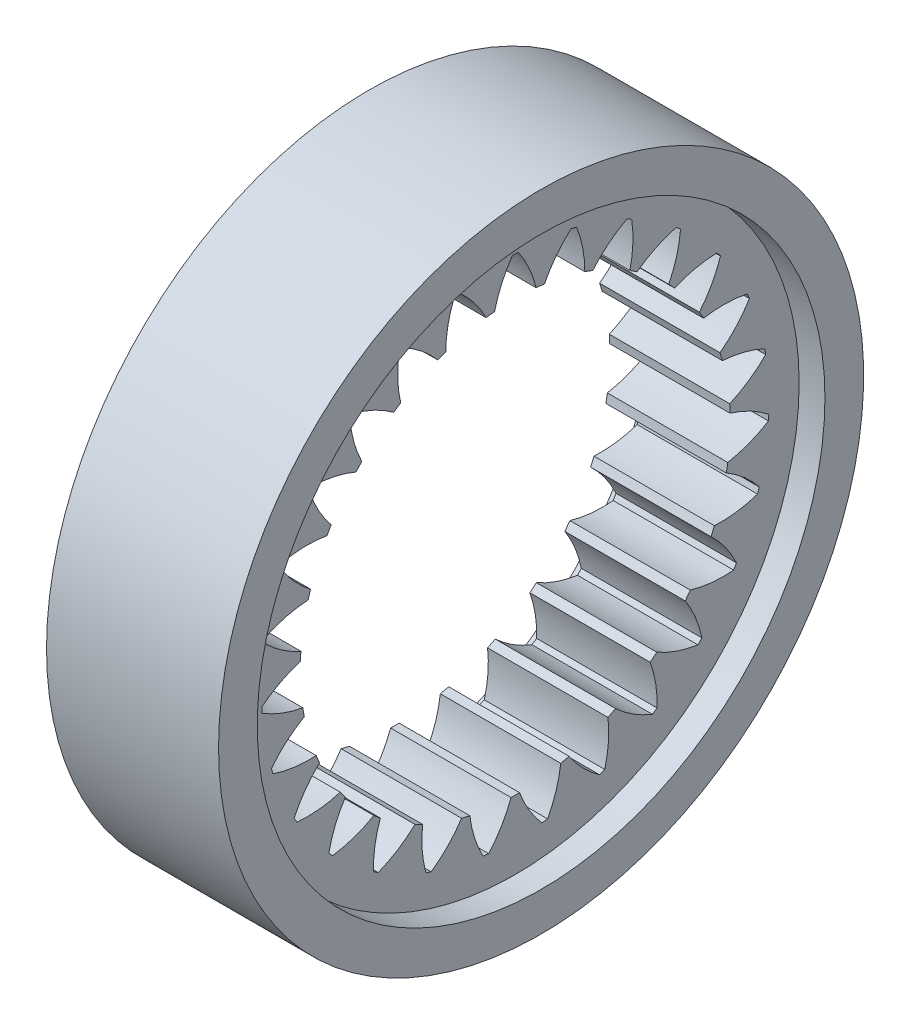
SolidWorks part; units mm, degrees
ref_plane "Plane1" through (0, 0, 0) normal (0, 0, 1) x (1, 0, 0)
ref_plane "Plane2" through (0, 0, 0) normal (0, 1, 0) x (1, 0, 0)
ref_plane "Plane3" through (0, 0, 0) normal (1, 0, 0) x (0, 0, -1)
other "Configuration Table"
sketch "HoldingSke" plane through (0, 0, 0) normal (0, 1, 0) x (1, 0, 0)
  line L0 (0, 0) -> (0.4455, -0.227)
  line L1 (-15, 0) -> (100, 0) construction
  line L2 (0, 0) -> (-2.1039, 2.3779)
  line L3 (0, 0) -> (-11.863, 4.5341)
  line L4 (0, 0) -> (7.6947, 3.9207)
  line L5 (0, 0) -> (-23.7986, -8.8762)
  line L6 (0, 0) -> (-10.5278, -7.1032)
  line L7 (-2.1039, 2.3779) -> (3.3635, 27.1825)
  line L8 (-76.2, 4.3779) -> (-54.61, 4.3779)
  line L9 (-71.009, 38.7566) -> (-53.1078, 45.2721)
  line L10 (-76.2, 71.12) -> (104.1128, 71.12)
  line L11 (0, 0) -> (-20, 0)
  line L12 (-76.2, 101.6) -> (-76.133, 101.6)
  line L13 (24.9733, 27.94) -> (52.9518, 28.4284)
  line L14 (24.9733, 27.94) -> (24.9743, 27.94)
  line L15 (24.9733, 27.94) -> (100.4006, 29.5858)
  circle A0 centre (0, 0) radius 37.5
  circle A1 centre (0, 0) radius 12.7
  circle A2 centre (0, 0) radius 12.7
  dimension "Num_teeth" = 27
  dimension "Pitch_radius" = 180.3128
  dimension "Width" = 20
  dimension "Diameter" = 75
sketch "BasProSke" plane through (0, 0, 0) normal (0, 1, 0) x (1, 0, 0)
  line L0 (-10, 0) -> (60, 0) construction
  line L1 (0, 25) -> (0, 37.5)
  line L2 (0, 25) -> (20, 25)
  line L3 (20, 25) -> (20, 37.5)
  line L4 (20, 37.5) -> (0, 37.5)
  dimension "Thickness" = 20
  dimension "Diameter" = 75
revolve "Base-Revolve" add sketch "BasProSke" angle 360 about L0
sketch "TooCutSke" plane through (0, 0, 0) normal (1, 0, 0) x (0, 0, -1)
  line L3 (1.7374, 26.944) -> (1.7374, 53.6633) construction
  line L4 (0, 0) -> (0, 59.563) construction
  line L5 (0, 0) -> (-7.9323, 67.8655) construction
  line L6 (-10.7181, 21.7372) -> (34.936, 27.0734) construction
  circle A0 centre (0, 0) radius 27 construction
  circle A1 centre (0, 0) radius 29.501 construction
  circle A2 centre (0, 0) radius 22.8345 construction
  circle A3 centre (0, 0) radius 24.9746 construction
  arc A4 (2.4164, 24.8574) -> (0.3274, 29.4992) centre (-10.7181, 21.7372) ccw
  arc A5 (2.4164, 24.8574) -> (-2.4164, 24.8574) centre (0, 0) ccw
  arc A6 (0.3274, 29.4992) -> (-0.3274, 29.4992) centre (0, 0) ccw
  arc A7 (-0.3274, 29.4992) -> (-2.4164, 24.8574) centre (10.7181, 21.7372) ccw
extrude "ToothCut" cut sketch "TooCutSke" along normal through all
fillet "Breaks" [suppressed] radius 0.2
fillet "RootFillets" [suppressed] radius 0.501
pattern_circular "TeethCuts" count 27 every 13.333 about axis through (-10, 0, 0) along (1, 0, 0) of "RootFillets", "Breaks", "ToothCut"
sketch "Sketch1" plane through (20, 0, 0) normal (1, 0, 0) x (0, 0, -1)
  circle A0 centre (0, 0) radius 33
  dimension "D1" = 66
extrude "Cut-Extrude1" cut sketch "Sketch1" against normal blind 3
sketch "Sketch2" plane through (0, 0, 0) normal (-1, 0, 0) x (0, 0, 1)
  circle A0 centre (0, 0) radius 33
  dimension "D1" = 66
extrude "Cut-Extrude2" cut sketch "Sketch2" against normal blind 3
equation "' \"Module@HoldingSke\" = 6.35"
equation "' \"Num_teeth@HoldingSke\" = 24"
equation "' \"Ap@HoldingSke\" =  14.5"
equation "' \"Ap@HoldingSke\" = 14.5"
equation "' \"Width@HoldingSke\" = 12"
equation "' \"Diameter@HoldingSke\" = 8 * 25.4"
equation "' \"Show_teeth@HoldingSke\" = 100"
equation "' \"Backlash@HoldingSke\" = 0.009 * 25.4"
equation "' \"Addendum_fac@HoldingSke\" = 1.0"
equation "' \"Dedendum_fac@HoldingSke\" = 1.25"
equation "' \"Dedendum_add@HoldingSke\" = 0.00005 * 25.4"
equation "' \"Clearance_fac@HoldingSke\" = 0.25"
equation "\"Pitch@HoldingSke\" = 1 / \"Module@HoldingSke\" "
equation "\"Overcut_dia@TooCutSke\" = (\"Num_teeth@HoldingSke\" - 2 * \"Addendum_fac@HoldingSke\") / \"Pitch@HoldingSke\" - 0.002 * 25.4"
equation "\"Pitch_dia@TooCutSke\" = \"Num_teeth@HoldingSke\" / \"Pitch@HoldingSke\""
equation "\"Base_dia@TooCutSke\" = \"Num_teeth@HoldingSke\" / \"Pitch@HoldingSke\" * cos((\"Ap@HoldingSke\"  * 3.14159265 / 180)) * 0.90"
equation "\"Root_dia@TooCutSke\" = \"Num_teeth@HoldingSke\"  / \"Pitch@HoldingSke\" + 2 *  \"Dedendum_fac@HoldingSke\"/ \"Pitch@HoldingSke\" + \"Dedendum_add@HoldingSke\" * 2"
equation "\"Half_ang@TooCutSke\" = 180 / \"Num_teeth@HoldingSke\""
equation "\"Half_CT@TooCutSke\" = \"Num_teeth@HoldingSke\" / \"Pitch@HoldingSke\" * sin((3.14159265 / 2 / \"Num_teeth@HoldingSke\")) / 2 + 10 * \"Backlash@HoldingSke\" / 4"
equation "\"Flank_rad@TooCutSke\" = \"Num_teeth@HoldingSke\" / \"Pitch@HoldingSke\" / 4"
equation "\"Radius@RootFillets\"= \"Clearance_fac@HoldingSke\" / \"Pitch@HoldingSke\" + \"Dedendum_add@HoldingSke\""
equation "\"Break_rad@Breaks\" = 0.02 / \"Pitch@HoldingSke\" * 5"
equation "\"Num_teeth@TeethCuts\" = int( \"Show_teeth@HoldingSke\" ) + 1"
equation "\"Num_teeth@TeethCuts\" = ((sgn( \"Num_teeth@TeethCuts\" - \"Num_teeth@HoldingSke\" )-1)*( \"Num_teeth@TeethCuts\" - \"Num_teeth@HoldingSke\" ))/-2+ \"Num_teeth@HoldingSke\""
equation "\"Num_teeth@TeethCuts\" = ((sgn( \"Num_teeth@TeethCuts\" - 2.0)+1)*( \"Num_teeth@TeethCuts\" - 2.0))/2 +2.0"
equation "\"Angle@TeethCuts\" = 360.0 / \"Num_teeth@HoldingSke\""
equation "\"Diameter@BasProSke\" = \"Num_teeth@HoldingSke\"  / \"Pitch@HoldingSke\" + 2 *  \"Dedendum_fac@HoldingSke\"/ \"Pitch@HoldingSke\" + \"Dedendum_add@HoldingSke\" * 2 + 0.002 * 25.4"
equation "\"Diameter@BasProSke\" = ((sgn( \"Diameter@BasProSke\"  - \"Diameter@HoldingSke\" )+1)*( \"Diameter@BasProSke\"  - \"Diameter@HoldingSke\" ))/2 + \"Diameter@HoldingSke\""
equation "\"Inside_diameter@BasProSke\" =  (\"Num_teeth@HoldingSke\" - 2 * \"Addendum_fac@HoldingSke\") / \"Pitch@HoldingSke\" "
equation "\"Thickness@BasProSke\"  = \"Width@HoldingSke\""
